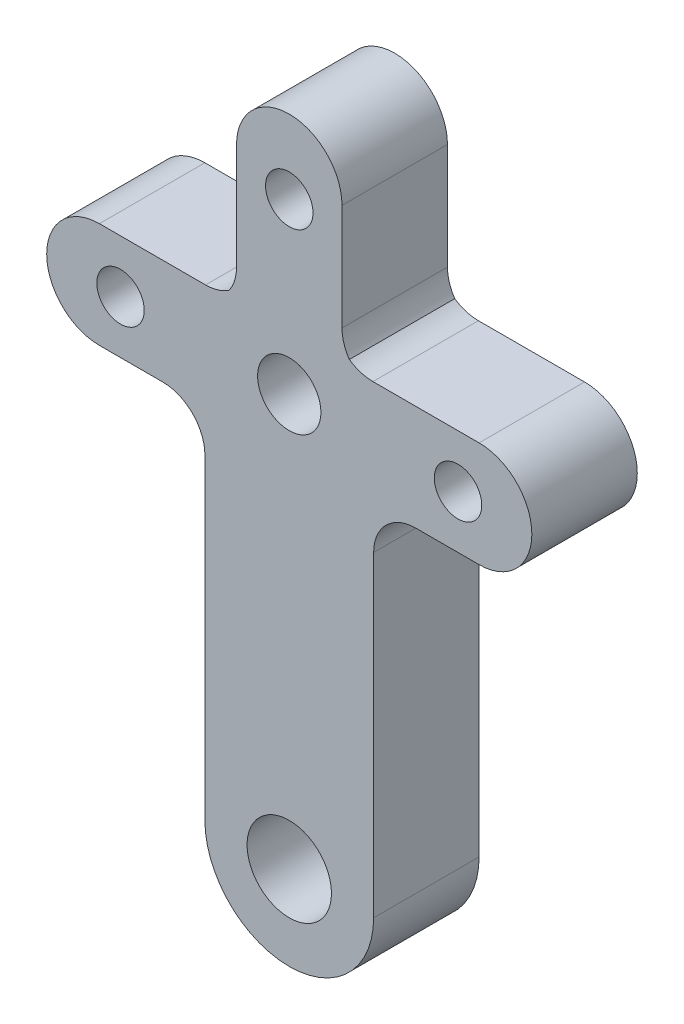
SolidWorks part; units mm, degrees
ref_plane "Plan de face" through (0, 0, 0) normal (0, 0, 1) x (1, 0, 0)
ref_plane "Plan de dessus" through (0, 0, 0) normal (0, 1, 0) x (1, 0, 0)
ref_plane "Plan de droite" through (0, 0, 0) normal (1, 0, 0) x (0, 0, -1)
sketch "Esquisse1" plane through (0, 0, 0) normal (0, 0, 1) x (1, 0, 0)
  circle A0 centre (0, 0) radius 26.25
  dimension "D1" = 52.5
extrude "Boss.-Extru.1" add sketch "Esquisse1" along normal blind 5
sketch "Esquisse2" plane through (0, 0, 5) normal (0, 0, 1) x (1, 0, 0)
  circle A0 centre (0, 0) radius 1.5
  dimension "D1" = 3
extrude "Enlèv. mat.-Extru.1" cut sketch "Esquisse2" against normal up to surface (5 mm away) up to face at (26.25, 0, 0)
sketch "Esquisse3" plane through (0, 0, 5) normal (0, 0, 1) x (1, 0, 0)
  line L0 (0, -19.5) -> (0, -17.5) construction
  line L3 (0, 0) -> (0, -19.5) construction
  line L6 (4, 0) -> (4, -19.5)
  line L9 (-4, 0) -> (-4, -19.5)
  line L12 (0, 0) -> (9, 0) construction
  line L13 (0, 2.5) -> (9, 2.5)
  line L14 (0, -2.5) -> (9, -2.5)
  line L18 (0, 0) -> (-9, 0) construction
  line L19 (0, -2.5) -> (-9, -2.5)
  line L20 (0, 2.5) -> (-9, 2.5)
  line L21 (0, 0) -> (0, 9) construction
  line L22 (-2.5, 0) -> (-2.5, 9)
  line L23 (2.5, 0) -> (2.5, 9)
  line L57 (0, 0) -> (0, -9) construction
  line L58 (2.5, 0) -> (2.5, -9)
  line L59 (-2.5, 0) -> (-2.5, -9)
  line L60 (0, 0) -> (0, -9) construction
  line L61 (2.5, 0) -> (2.5, -9)
  line L62 (-2.5, 0) -> (-2.5, -9)
  circle A0 centre (0, -19.5) radius 2
  circle A1 centre (0, 0) radius 1.5 construction
  arc A2 (4, 0) -> (-4, 0) centre (0, 0) ccw
  arc A3 (-4, -19.5) -> (4, -19.5) centre (0, -19.5) ccw
  arc A4 (0, 2.5) -> (0, -2.5) centre (0, 0) ccw
  arc A5 (9, -2.5) -> (9, 2.5) centre (9, 0) ccw
  arc A8 (0, -2.5) -> (0, 2.5) centre (0, 0) ccw
  arc A9 (-9, 2.5) -> (-9, -2.5) centre (-9, 0) ccw
  arc A10 (-2.5, 0) -> (2.5, 0) centre (0, 0) ccw
  arc A11 (2.5, 9) -> (-2.5, 9) centre (0, 9) ccw
  circle A15 centre (0, 0) radius 26.25
  circle A16 centre (0, 0) radius 26.25
  arc A39 (2.5, 0) -> (-2.5, 0) centre (0, 0) ccw
  arc A40 (-2.5, -9) -> (2.5, -9) centre (0, -9) ccw
  point P2 (0, -6.5)
  point P6 (0, -9.75)
  point P11 (0, 7.6855)
  point P15 (4.5, 0)
  point P18 (-8.3537, 0)
  point P23 (0.001, -5.499)
  point P26 (6.9416, 0)
  point P34 (-4.5, 0)
  point P42 (0, 4.5)
  point P47 (0, 0)
  point P54 (0.001, -5.499)
  point P61 (0.001, -5.499)
  point P68 (0.001, -5.499)
  point P75 (0.001, -5.499)
  point P82 (0.001, -5.499)
  point P89 (0.001, -5.499)
  point P96 (0.001, -5.499)
  point P103 (0, -4.5)
  point P110 (0, -4.5)
  point P117 (0, -4.5)
  point P124 (0, -4.5)
  point P131 (0, -4.5)
  circle M3 centre (0, 0) radius 26.25
  dimension "D1" = 4
  dimension "D2" = 19.5
  dimension "D3" = 2
  dimension "D4" = 5
  dimension "D5" = 9
  dimension "D7" = 0
  dimension "D6" = 4
extrude "Enlèv. mat.-Extru.2" cut sketch "Esquisse3" against normal up to surface (5 mm away) contours A11 L23 A2 L13 A5 L14 L6 A3 L9 L19 A9 L20 L22 M3 | A0 region at (0, -19.5, 5) region at (-25.5075, 0, 5) up to face at (1.5, 0, 0)
fillet "Congé1" radius 2 6 edges at (-4, -2.5, 2.5) (-3.1225, 2.5, 2.5) (-2.5, 3.1225, 2.5) (3.1225, 2.5, 2.5) (2.5, 3.1225, 2.5) (4, -2.5, 2.5)
sketch "Esquisse4" plane through (0, 0, 5) normal (0, 0, 1) x (1, 0, 0)
  line L0 (-8, 0) -> (8, 0)
  circle A1 centre (-8, 0) radius 1.125
  circle A2 centre (8, 0) radius 1.125
  circle A3 centre (0, -8) radius 1.125
  circle A4 centre (-8, 0) radius 1.125
  circle A5 centre (0, 8) radius 1.125
  point P6 (0, 0)
  point P17 (0, 0)
  dimension "D2" = 2.25
  dimension "D3" = 2.25
  dimension "D1" = 16
  dimension "D5" = 8
  dimension "D4" = 4
extrude "Enlèv. mat.-Extru.3" cut sketch "Esquisse4" against normal blind 10 contours A1 | A5 | A2 region at (8, 1.0932, 5) region at (-9.0932, 0, 5) region at (0, 8, 5)
